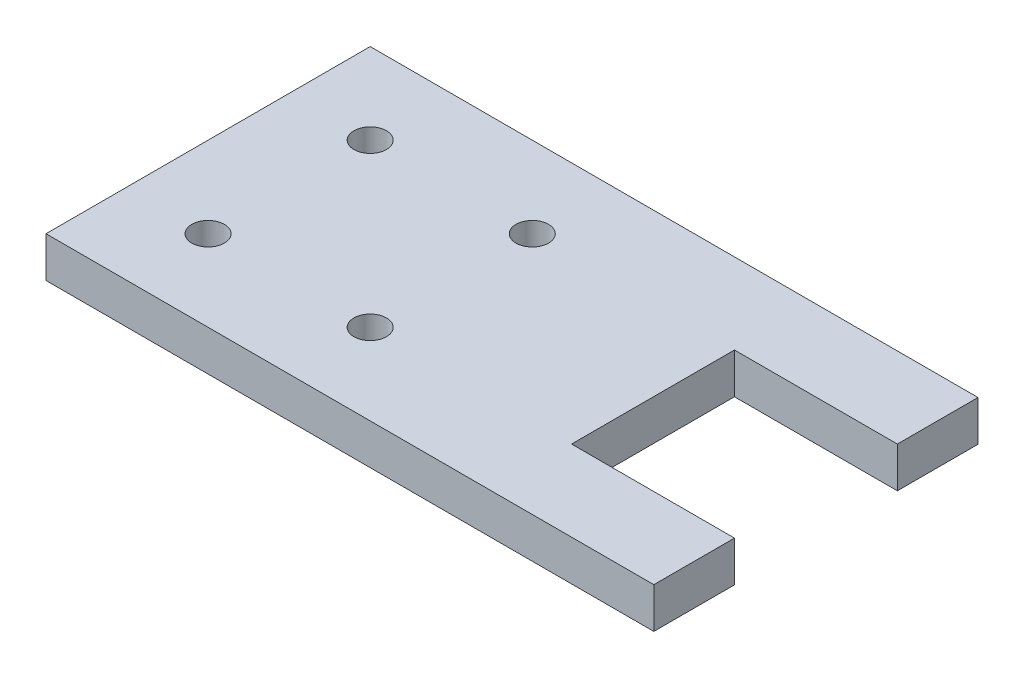
SolidWorks part; units mm, degrees
material "6061-T6 (SS)"
ref_plane "Front Plane" through (0, 0, 0) normal (0, 0, 1) x (1, 0, 0)
ref_plane "Top Plane" through (0, 0, 0) normal (0, 1, 0) x (1, 0, 0)
ref_plane "Right Plane" through (0, 0, 0) normal (1, 0, 0) x (0, 0, -1)
sketch "Sketch1" plane through (0, 0, 0) normal (0, 1, 0) x (1, 0, 0)
  line L0 (34.925, 25.4) -> (60.325, 25.4)
  line L1 (-34.925, -25.4) -> (34.925, -25.4)
  line L2 (-34.925, -25.4) -> (-34.925, 25.4)
  line L3 (-34.925, 25.4) -> (34.925, 25.4)
  line L5 (-34.925, -25.4) -> (34.925, 25.4) construction
  line L6 (-34.925, 25.4) -> (34.925, -25.4) construction
  line L7 (60.325, 25.4) -> (60.325, -25.4)
  line L8 (60.325, -25.4) -> (34.925, -25.4)
  point P0 (0, 0)
  dimension "D1" = 69.85
  dimension "D2" = 50.8
  dimension "D3" = 25.4
extrude "Boss-Extrude1" add sketch "Sketch1" along normal blind 6.35
sketch "Sketch2" plane through (0, 6.35, 0) normal (0, 1, 0) x (1, 0, 0)
  line L4 (60.325, 25.4) -> (-34.925, 25.4) construction
  line L5 (-34.925, -25.4) -> (60.325, -25.4) construction
  line L7 (15.875, 25.4) -> (15.875, -25.4) construction
  line L8 (-34.925, 25.4) -> (-34.925, -25.4) construction
  dimension "D1" = 50.8
hole_wizard "#10 Clearance Hole1" positions "Sketch3" profile "Sketch4" hole size "#10" standard "ANSI Inch" end condition through all
sketch "Sketch3" plane through (0, 6.35, 0) normal (0, 1, 0) x (1, 0, 0)
  line L4 (-22.225, 25.4) -> (-22.225, -25.4) construction
  line L5 (60.325, 25.4) -> (-34.925, 25.4) construction
  line L6 (-34.925, -25.4) -> (60.325, -25.4) construction
  line L8 (3.175, 25.4) -> (3.175, -25.4) construction
  line L9 (-34.925, 25.4) -> (-34.925, -25.4) construction
  line L11 (-34.925, 12.7) -> (15.875, 12.7) construction
  line L13 (-34.925, -12.7) -> (15.875, -12.7) construction
  point P0 (-22.225, 12.7)
  point P2 (3.175, 12.7)
  point P4 (3.175, -12.7)
  point P6 (-22.225, -12.7)
  dimension "D1" = 12.7
  dimension "D2" = 38.1
  dimension "D3" = 12.7
  dimension "D4" = 12.7
  dimension "D5" = 50.8
  dimension "D6" = 50.8
sketch "Sketch4" plane through (-22.225, 6.35, -12.7) normal (1, 0, 0) x (0, 0, 1)
  line L0 (0, 0) -> (0, 6.35)
  line L1 (0, 6.35) -> (2.5527, 6.35)
  line L2 (2.5527, 6.35) -> (2.5527, 0)
  line L5 (2.5527, 0) -> (0, 0)
  line L11 (0, -6.35) -> (0, 107.95) construction
  dimension "Thru Hole Dia." = 5.1054
  dimension "Thru Hole Depth" = 6.35
sketch "Sketch5" plane through (0, 6.35, 0) normal (0, 1, 0) x (1, 0, 0)
  line L1 (60.325, -25.4) -> (60.325, 25.4) construction
  line L2 (34.798, -12.7635) -> (60.325, -12.7635)
  line L4 (34.798, -12.7635) -> (34.798, 12.7635)
  line L5 (34.798, 12.7635) -> (60.325, 12.7635)
  line L6 (60.325, -12.7635) -> (60.325, 12.7635)
  line L7 (34.798, -12.7635) -> (60.325, 12.7635) construction
  line L8 (34.798, 12.7635) -> (60.325, -12.7635) construction
  line L13 (60.325, 12.7635) -> (60.325, 25.4) construction
  line L14 (60.325, -12.7635) -> (60.325, -25.4) construction
  dimension "D3" = 25.527
extrude "Cut-Extrude1" cut sketch "Sketch5" against normal through all
